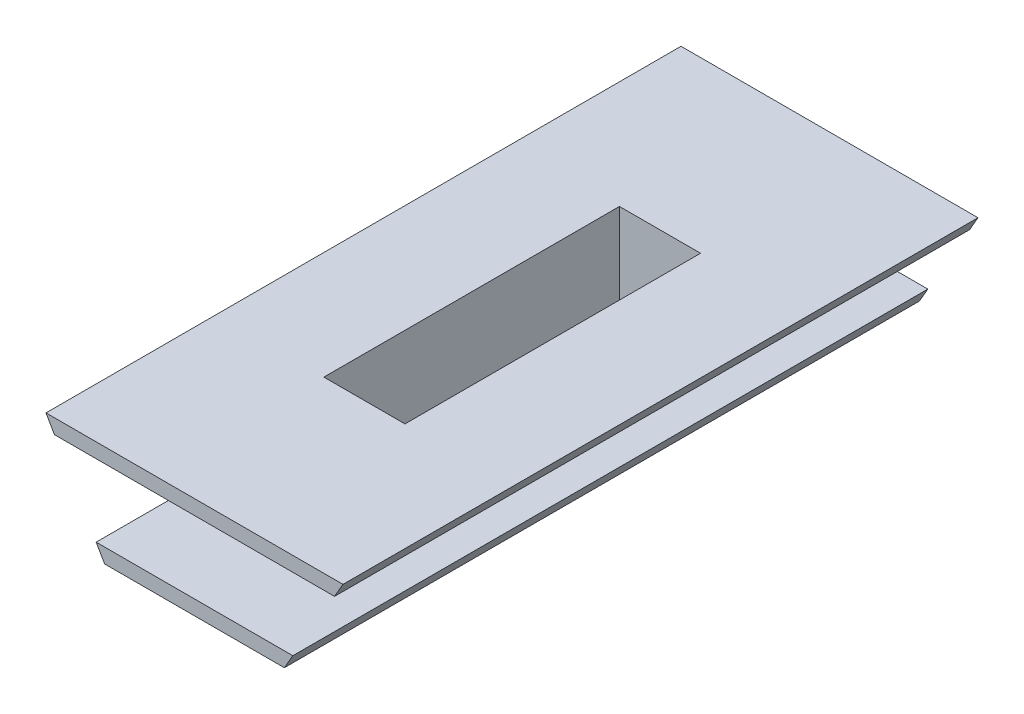
SolidWorks part; units mm, degrees
ref_plane "Front Plane" through (0, 0, 0) normal (0, 0, 1) x (1, 0, 0)
ref_plane "Top Plane" through (0, 0, 0) normal (0, 1, 0) x (1, 0, 0)
ref_plane "Right Plane" through (0, 0, 0) normal (1, 0, 0) x (0, 0, -1)
sketch "Casing" plane through (0, 0, 0) normal (0, 0, 1) x (1, 0, 0)
  line L0 (9.2, 0) -> (-9.2, 0)
  line L2 (0, 1.5) -> (0, 5.1962) construction
  line L4 (-9.2, 0) -> (-10.066, 1.5)
  line L5 (-15.2, 10.3923) -> (15.2, 10.3923)
  line L8 (9.2, 0) -> (10.066, 1.5)
  line L10 (-12.6019, 8.8923) -> (-5.15, 8.8923)
  line L12 (8.334, 1.5) -> (5.15, 1.5)
  line L14 (-14.334, 8.8923) -> (-5.15, 8.8923)
  line L16 (-10.066, 1.5) -> (-5.15, 1.5)
  line L17 (-14.334, 8.8923) -> (-15.2, 10.3923)
  line L18 (-9.2, 0) -> (-15.2, 10.3923) construction
  line L19 (14.334, 8.8923) -> (15.2, 10.3923)
  line L20 (9.2, 0) -> (15.2, 10.3923) construction
  line L21 (0, 5.1962) -> (-4.15, 5.1962) construction
  line L22 (-4.15, 8.8923) -> (-4.15, 1.5)
  line L23 (4.15, 8.8923) -> (4.15, 1.5)
  line L24 (-5.15, 8.8923) -> (-5.15, 1.5)
  line L25 (5.15, 8.8923) -> (5.15, 1.5)
  line L26 (-8.334, 1.5) -> (-12.6019, 8.8923) construction
  line L27 (8.334, 1.5) -> (12.6019, 8.8923) construction
  line L28 (4.15, 1.5) -> (-4.15, 1.5)
  line L29 (8.334, 1.5) -> (-8.334, 1.5) construction
  line L30 (5.15, 1.5) -> (10.066, 1.5)
  line L31 (5.15, 8.8923) -> (12.6019, 8.8923)
  line L32 (-12.6019, 8.8923) -> (12.6019, 8.8923) construction
  line L33 (5.15, 8.8923) -> (14.334, 8.8923)
  line L34 (-4.15, 1.5) -> (4.15, 1.5)
  line L35 (-5.15, 1.5) -> (-8.334, 1.5)
  line L36 (-4.15, 8.8923) -> (4.15, 8.8923)
  line L37 (-4.15, 8.8923) -> (4.15, 8.8923)
  line L38 (-12.6019, 8.8923) -> (-14.334, 8.8923)
  line L40 (12.6019, 8.8923) -> (14.334, 8.8923)
  line L41 (8.334, 1.5) -> (10.066, 1.5)
  point P8 (0, 10.3923)
  point P15 (0, 8.8923)
  point P18 (0, 1.5)
  point P22 (-4.15, 5.1962)
  dimension "D1" = 15.2
  dimension "D3" = 120
  dimension "D5" = 4.15
  dimension "D6" = 1
  dimension "D7" = 1
  dimension "D4" = 1.5
extrude "Boss-Extrude2" add sketch "Casing" along normal blind 65 contours L31 L33 L19 L5 L17 L14 L10 L24 L16 L4 L0 L8 L30 L12 L25 L22 L36 L23 L28 | L36 L22 L28 L23 region at (0, 0.3213, 0) region at (0, 5.1962, 0)
sketch "Sketch10" plane through (0, 0, 65) normal (0, 0, 1) x (1, 0, 0)
  line L0 (-5.15, 1.5) -> (5.15, 1.5)
  line L1 (-5.15, 1.5) -> (-5.15, 8.8924)
  line L2 (5.15, 1.5) -> (5.15, 8.8924)
  line L3 (-5.15, 8.8924) -> (5.15, 8.8924)
extrude "Top_Cut" cut sketch "Sketch10" against normal blind 16.35
sketch "Sketch11" plane through (0, 0, 0) normal (0, 0, -1) x (-1, 0, 0)
  line L0 (-5.15, 1.5) -> (5.15, 1.5)
  line L1 (-5.15, 1.5) -> (-5.15, 8.9052)
  line L2 (5.15, 1.5) -> (5.15, 8.9052)
  line L3 (-5.15, 8.9052) -> (5.15, 8.9052)
extrude "Bot_Cut" cut sketch "Sketch11" against normal blind 16.35
sketch "Sketch13" plane through (0, 10.3923, 0) normal (0, 1, 0) x (1, 0, 0)
  line L0 (-5.15, -16.35) -> (5.15, -16.35)
  line L1 (-5.15, -16.35) -> (-5.15, -48.6057)
  line L2 (5.15, -16.35) -> (5.15, -48.6057)
  line L3 (-5.15, -48.6057) -> (5.15, -48.6057)
  line L4 (-4.15, -17.35) -> (4.15, -17.35)
  line L5 (4.15, -17.35) -> (4.15, -47.6057)
  line L6 (-4.15, -47.6057) -> (4.15, -47.6057)
  line L7 (-4.15, -17.35) -> (-4.15, -47.6057)
  dimension "D1" = 1
extrude "Cut-Extrude8" cut sketch "Sketch13" against normal through all contours L4 L5 L6 L7
